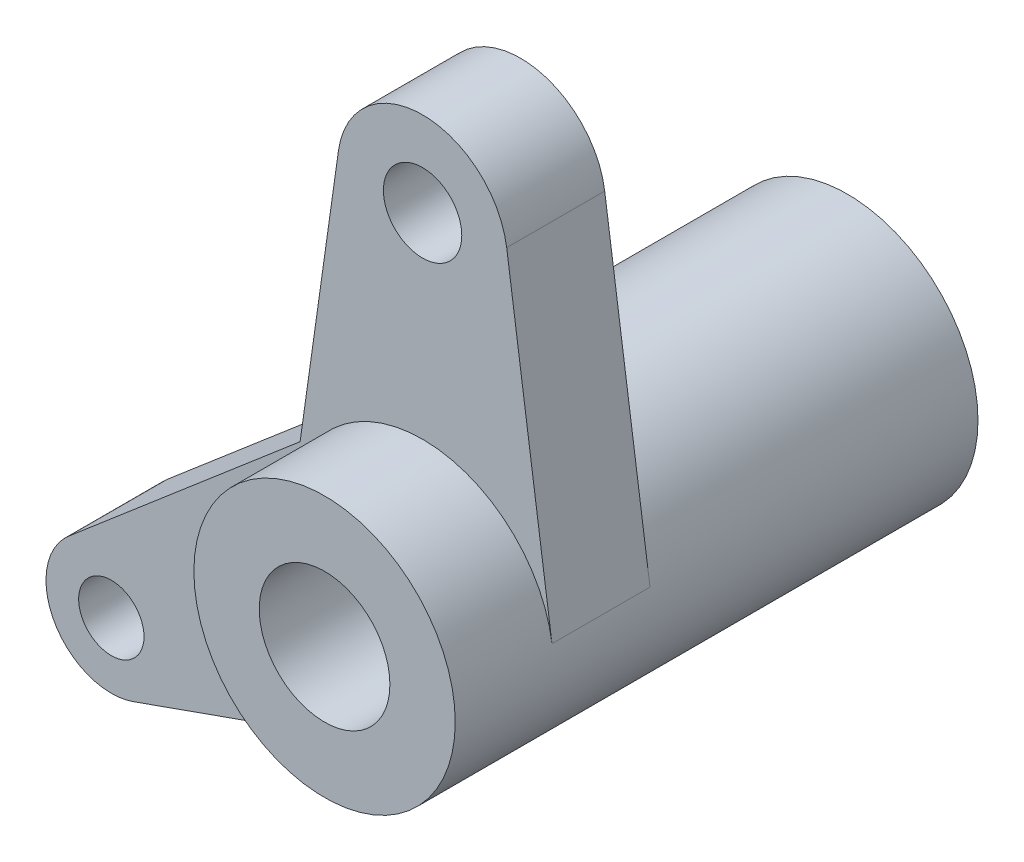
SolidWorks part; units mm, degrees
ref_plane "Спереди" through (0, 0, 0) normal (0, 0, 1) x (1, 0, 0)
ref_plane "Сверху" through (0, 0, 0) normal (0, 1, 0) x (1, 0, 0)
ref_plane "Справа" through (0, 0, 0) normal (1, 0, 0) x (0, 0, -1)
sketch "Эскиз1" plane through (0, 0, 0) normal (0, 0, 1) x (1, 0, 0)
  line L0 (0, 0) -> (-47.6314, -27.5) construction
  line L1 (-54.1226, -19.8932) -> (-12.9825, 15.2136)
  line L2 (-44.2893, -36.925) -> (6.6841, -18.85)
  line L3 (12.872, 51.82) -> (19.803, 2.8)
  line L4 (-12.872, 51.82) -> (-19.803, 2.8)
  line L5 (0, 0) -> (0, 50) construction
  circle A0 centre (0, 0) radius 10
  circle A1 centre (0, 0) radius 20
  circle A2 centre (0, 50) radius 13
  circle A3 centre (-47.6314, -27.5) radius 10
  circle A4 centre (0, 50) radius 6
  circle A5 centre (-47.6314, -27.5) radius 5
  dimension "D1" = 20
  dimension "D2" = 40
  dimension "D3" = 20
  dimension "D6" = 12
  dimension "D7" = 26
  dimension "D9" = 10
  dimension "D4" = 120
  dimension "D5" = 50
  dimension "D8" = 55
extrude "Бобышка-Вытянуть1" add sketch "Эскиз1" against normal blind 80 contours A1 A0 region at (6.8817, 18.1751, 0)
extrude "Бобышка-Вытянуть2" add sketch "Эскиз1<3>" against normal blind 15 from offset 15 contours A2 L4 L1 A1 L3 | A1 L1 L4 | A2 A4 | A3 L2 A1 L4 L1 | A3 A5 region at (-26.9848, -15.7307, 0) region at (-43.5613, -18.6763, 0) region at (0.1549, 28.0972, 0) region at (-17.7813, 9.7697, 0) region at (0, 62.6323, 0) offset against normal yes
sketch "Эскиз1<3>" plane through (0, 0, 0) normal (0, 0, 1) x (1, 0, 0) same geometry as "Эскиз1"
